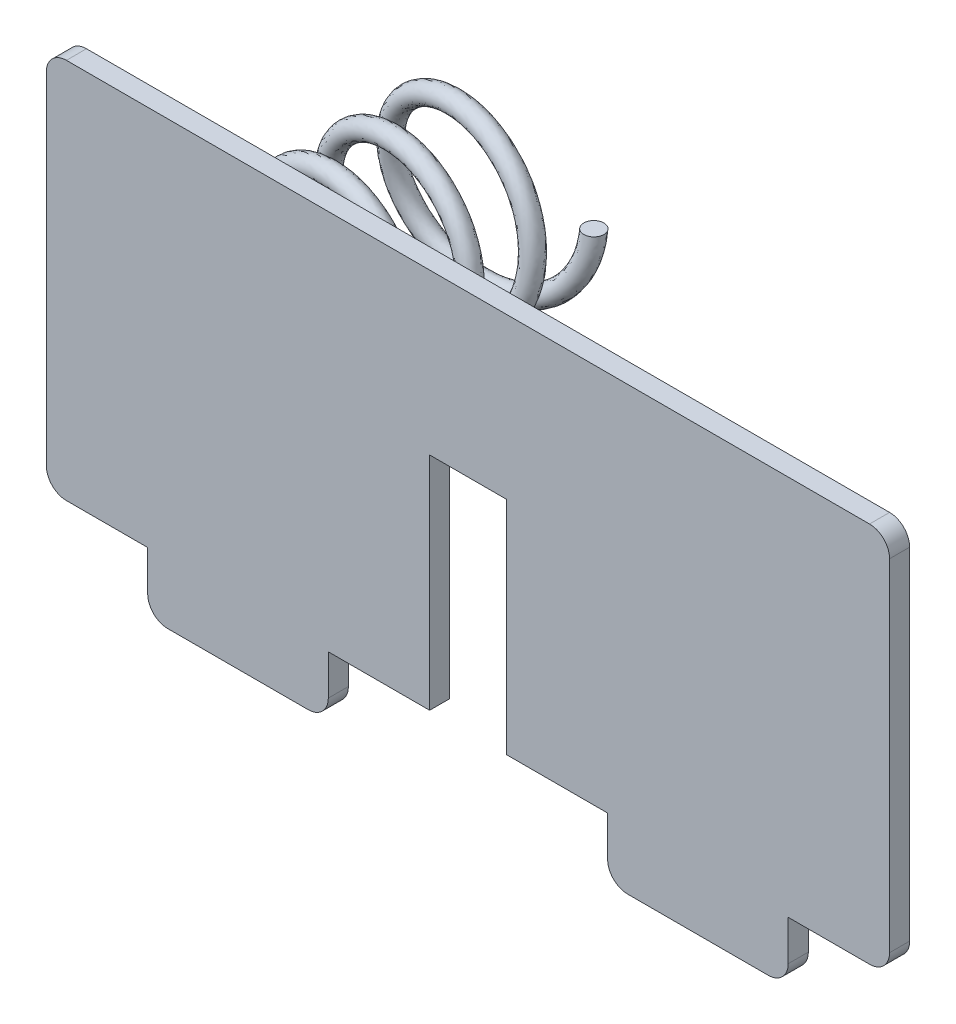
SolidWorks part; units mm, degrees
ref_plane "Front" through (0, 0, 0) normal (0, 0, 1) x (1, 0, 0)
ref_plane "Top" through (0, 0, 0) normal (0, 1, 0) x (1, 0, 0)
ref_plane "Right" through (0, 0, 0) normal (1, 0, 0) x (0, 0, -1)
sketch "Sketch1" plane through (0, 0, 0) normal (0, 0, 1) x (1, 0, 0)
  line L0 (0, 0) -> (21.01, 0)
  line L1 (21.01, 0) -> (21.01, -9.5)
  line L2 (21.01, -9.5) -> (18.485, -9.5)
  line L3 (18.485, -9.5) -> (18.485, -11)
  line L4 (18.485, -11) -> (13.985, -11)
  line L5 (13.985, -11) -> (13.985, -9.5)
  line L6 (13.985, -9.5) -> (11.46, -9.5)
  line L7 (11.46, -9.5) -> (11.46, -3.99)
  line L8 (11.46, -3.99) -> (9.55, -3.99)
  line L9 (9.55, -3.99) -> (9.55, -9.5)
  line L10 (9.55, -9.5) -> (7.025, -9.5)
  line L11 (7.025, -9.5) -> (7.025, -11)
  line L12 (7.025, -11) -> (2.525, -11)
  line L13 (2.525, -11) -> (2.525, -9.5)
  line L14 (2.525, -9.5) -> (0, -9.5)
  line L15 (0, -9.5) -> (0, 0)
  line L16 (4.775, -11) -> (4.775, -3.51) construction
  line L17 (16.2414, -11.4894) -> (16.2414, -3.51) construction
  line L18 (4.775, -3.51) -> (16.2414, -3.51) construction
  circle A0 centre (4.775, -3.51) radius 1.2643
  circle A1 centre (16.2414, -3.5113) radius 1.2643
  dimension "D1" = 21.01
  dimension "D2" = 4.5
  dimension "D3" = 9.55
  dimension "D4" = 1.5
  dimension "D5" = 7.01
  dimension "D6" = 11
  dimension "D7" = 7.49
extrude "Boss-Extrude1" add sketch "Sketch1" along normal blind 0.5 contours L15 L14 L13 L12 L11 L10 L9 L8 L7 L6 L5 L4 L3 L2 L1 L0 A1 A0 | A0 | A1 region at (10.505, -0.2372, 0) region at (4.775, -3.51, 0) region at (16.2414, -3.5113, 0)
extrude "Boss-Extrude2" add sketch "Sketch1<3>" against normal blind 0.5 contours A1 | A0 region at (4.775, -3.51, 0) region at (16.2414, -3.5113, 0)
sketch "Sketch1<3>" plane through (0, 0, 0) normal (0, 0, 1) x (1, 0, 0) same geometry as "Sketch1"
chamfer "Chamfer1" distance 0.5 angle 45 2 edges at (6.0393, -3.51, 0) (17.5056, -3.5113, 0)
sketch "Sketch2" plane through (0, 0, 0) normal (0, 0, -1) x (-1, 0, 0)
  circle A0 centre (-4.8319, -3.7353) radius 2.1372
curve "Helix/Spiral1" pitch 1.5431 height 6.1722 radius 2.1372 left hand yes centre (4.8319, -3.7353, 0) axis (0, 0, -1) start towards (1, 0, 0)
ref_plane "Plane1" through (0, -3.7353, 0) normal (0, -1, 0) x (-1, 0, 0)
sketch "Sketch3" plane through (0, -3.7353, 0) normal (0, -1, 0) x (-1, 0, 0)
  circle A0 centre (-6.9691, 0) radius 0.25
  dimension "D1" = 0.5
sweep "Sweep1" add profiles "Sketch3" path "Helix/Spiral1"
fillet "Fillet1" radius 0.5 8 edges at (21.01, -9.5, 0.25) (18.485, -11, 0.25) (13.985, -11, 0.25) (7.025, -11, 0.25) (2.525, -11, 0.25) (0, -9.5, 0.25) (0, 0, 0.25) (21.01, 0, 0.25)
ref_plane "Plane2" through (10.505, 0, 0) normal (-1, 0, 0) x (0, 0, 1)
ref_plane "Plane3" through (0, 0, 0.25) normal (0, 0, -1) x (-1, 0, 0)
ref_axis "Axis1" through (10.505, -11.55, 0.25) along (0, 1, 0)
ref_point "Point1"
